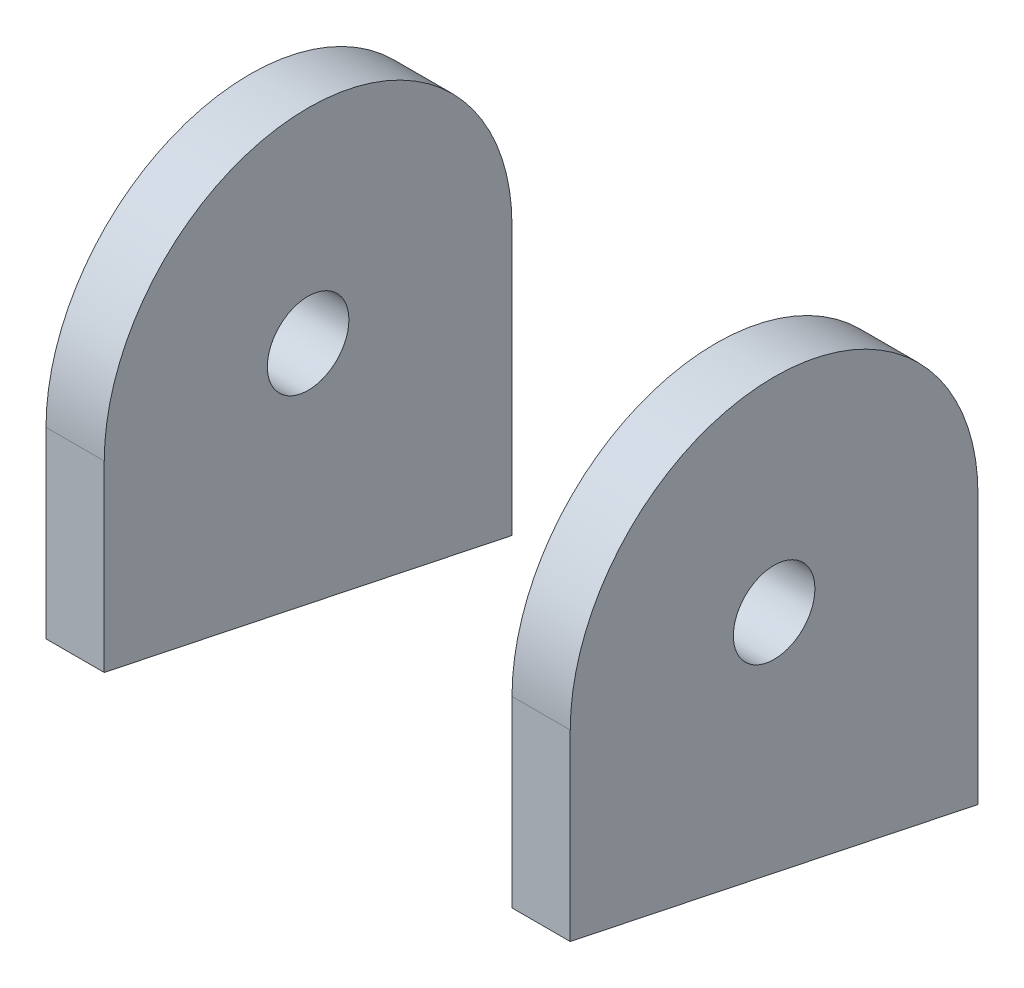
SolidWorks part; units mm, degrees
ref_plane "前视基准面" through (0, 0, 0) normal (0, 0, 1) x (1, 0, 0)
ref_plane "上视基准面" through (0, 0, 0) normal (0, 1, 0) x (1, 0, 0)
ref_plane "右视基准面" through (0, 0, 0) normal (1, 0, 0) x (0, 0, -1)
sketch "草图1" plane through (0, 0, 0) normal (1, 0, 0) x (0, 0, -1)
  line L1 (35, 0) -> (35, -100)
  line L2 (-35, 0) -> (-35, -100)
  line L3 (-35, -100) -> (35, -100)
  circle A0 centre (0, 0) radius 7
  arc A1 (35, 0) -> (-35, 0) centre (0, 0) ccw
extrude "凸台-拉伸1" add sketch "草图1" along normal blind 10 and the other way blind 80
extrude "切除-拉伸1" cut sketch "草图1<2>" against normal blind 70
sketch "草图1<2>" plane through (0, 0, 0) normal (1, 0, 0) x (0, 0, -1) same geometry as "草图1"
sketch "草图2" plane through (0, -37.144, 7.762) normal (0, 0.9789, -0.2046) x (-1, 0, 0)
  circle A0 centre (0, 0) radius 199.3663
extrude "切除-拉伸4" cut sketch "草图2" against normal blind 284.6875
